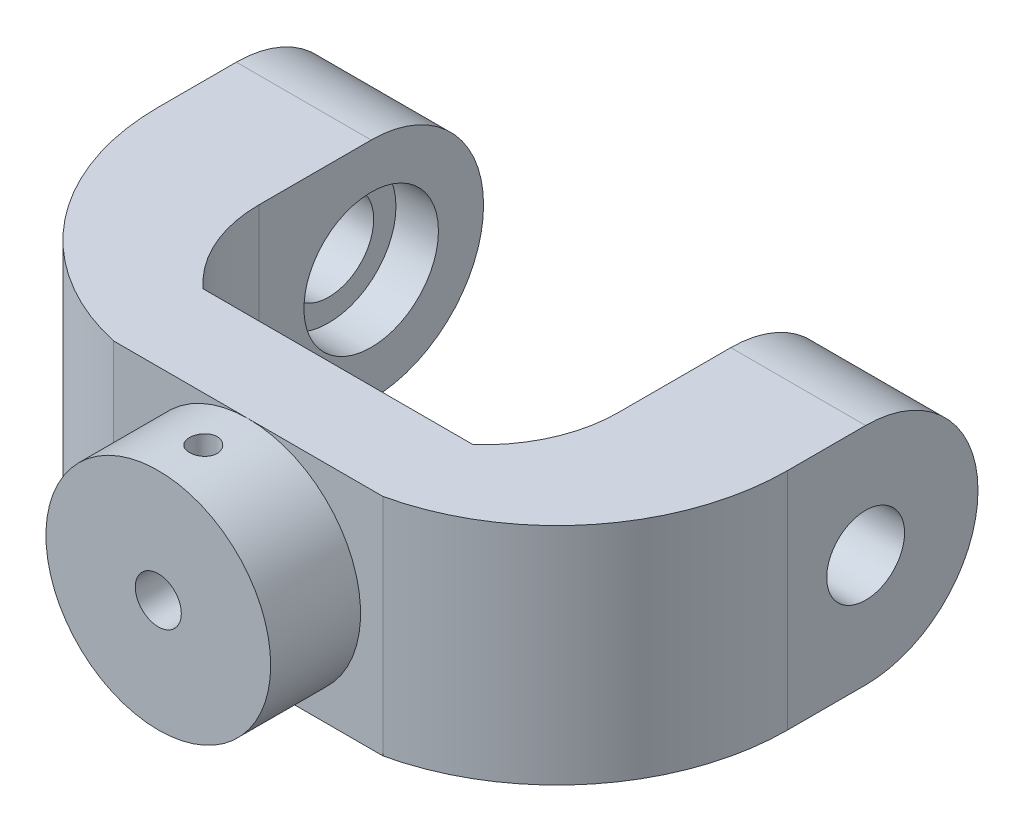
SolidWorks part; units mm, degrees
material "PLA"
ref_plane "Front Plane" through (0, 0, 0) normal (0, 0, 1) x (1, 0, 0)
ref_plane "Top Plane" through (0, 0, 0) normal (0, 1, 0) x (1, 0, 0)
ref_plane "Right Plane" through (0, 0, 0) normal (1, 0, 0) x (0, 0, -1)
sketch "Sketch1" plane through (0, 0, 0) normal (0, 0, 1) x (1, 0, 0)
  line L1 (-19.05, -15.875) -> (19.05, -15.875)
  line L2 (-19.05, -15.875) -> (-19.05, 15.875)
  line L3 (-19.05, 15.875) -> (19.05, 15.875)
  line L4 (19.05, -15.875) -> (19.05, 15.875)
  line L5 (-19.05, -15.875) -> (19.05, 15.875) construction
  line L6 (-19.05, 15.875) -> (19.05, -15.875) construction
  circle A0 centre (0, 0) radius 15.875
  circle A2 centre (0, 0) radius 3.25
  dimension "D1" = 31.75
  dimension "D3" = 6.5
  dimension "D4" = 31.75
  dimension "D5" = 38.1
extrude "Boss-Extrude1" add sketch "Sketch1" along normal blind 12.7 contours A0 region at (-15.426, 0, 0)
extrude "Boss-Extrude2" add sketch "Sketch1<3>" against normal blind 12.7 contours A0 | A0 | A0 L3 L2 L1 region at (-18.6797, 0, 0) region at (11.4871, -11.4871, 0) region at (-15.426, 0, 0)
sketch "Sketch1<3>" plane through (0, 0, 0) normal (0, 0, 1) x (1, 0, 0) same geometry as "Sketch1"
ref_plane "Plane1" through (0, 15.875, 0) normal (0, 1, 0) x (1, 0, 0)
sketch "Sketch4" plane through (0, 15.875, 0) normal (0, 1, 0) x (1, 0, 0)
  line L0 (-15.875, -12.7) -> (15.875, -12.7) construction
  line L1 (0, 0) -> (15.875, 0) construction
  line L2 (-15.875, -12.7) -> (15.875, -12.7)
  line L3 (0, 0) -> (15.875, 0)
  line L4 (0, 0) -> (0, -12.7) construction
  circle A0 centre (0, -6.35) radius 1.95
  point P4 (0, -9.525)
  dimension "D1" = 3.9
extrude "Cut-Extrude1" cut sketch "Sketch4" against normal up to surface (12.625 mm away) contours A0 L4 | L4 A0 region at (0.8276, 15.875, 6.35) region at (-0.8276, 15.875, 6.35) up to face at (3.25, 0, 12.7)
sketch "Sketch6" plane through (0, 15.875, 0) normal (0, 1, 0) x (1, 0, 0)
  line L5 (-19.05, 0) -> (0, 0)
  line L6 (0, 0) -> (19.05, 0)
  line L7 (19.05, 0) -> (19.05, 12.7)
  line L8 (19.05, 12.7) -> (-19.05, 12.7)
  line L9 (-19.05, 12.7) -> (-19.05, 0)
  line L10 (-19.05, 0) -> (0, 0)
  line L11 (0, 0) -> (19.05, 0)
  line L12 (19.05, 0) -> (19.05, 12.7)
  line L13 (19.05, 12.7) -> (-19.05, 12.7)
  line L14 (-19.05, 12.7) -> (-19.05, 0)
  dimension "D1" = 0
sketch "Sketch7" plane through (0, 15.875, 0) normal (0, 1, 0) x (1, 0, 0)
  line L0 (-44.45, 58.649) -> (-25.4, 58.649)
  line L1 (-19.05, 0) -> (0, 0) construction
  line L2 (-44.45, 31.75) -> (-44.45, 58.649)
  line L3 (-25.4, 26.899) -> (-25.4, 58.649)
  line L9 (-19.05, 0) -> (0, 0)
  line L10 (0, 0) -> (19.05, 0)
  line L11 (19.05, 0) -> (19.05, 12.7)
  line L12 (19.05, 12.7) -> (-19.05, 12.7)
  line L13 (-19.05, 12.7) -> (-19.05, 0)
  line L14 (-19.05, 0) -> (0, 0)
  line L15 (0, 0) -> (19.05, 0)
  line L16 (19.05, 0) -> (19.05, 12.7)
  line L17 (19.05, 12.7) -> (-19.05, 12.7)
  arc A0 (-19.05, 0) -> (-44.45, 31.75) centre (-11.9062, 31.75) cw
  arc A1 (-19.05, 12.7) -> (-25.4, 26.899) centre (-6.35, 26.899) cw
  line M7 (-19.05, 12.7) -> (-19.05, 0)
  dimension "D1" = 31.75
  dimension "D2" = 31.75
  dimension "D4" = 19.05
  dimension "D3" = 44.45
  dimension "D5" = 19.05
  dimension "D6" = 0
extrude "Boss-Extrude3" add sketch "Sketch7" against normal up to surface (31.75 mm away) contours A1 L3 L0 L2 A0 M7 region at (-33.015, 15.875, -31.5973) up to face at (0, -15.875, -5.08)
fillet "Fillet1" radius 15.875 2 edges at (-34.925, -15.875, -58.649) (-34.925, 15.875, -58.649)
sketch "Sketch8" plane through (-25.4, 0, 0) normal (1, 0, 0) x (0, 0, -1)
  line L3 (26.899, -15.875) -> (42.774, -15.875)
  line L4 (42.774, 15.875) -> (26.899, 15.875)
  line L5 (26.899, 15.875) -> (26.899, -15.875)
  line L6 (26.899, -15.875) -> (42.774, -15.875)
  line L7 (42.774, 15.875) -> (26.899, 15.875)
  line L8 (26.899, 15.875) -> (26.899, -15.875)
  circle A0 centre (42.774, 0) radius 9.5
  circle A1 centre (42.774, 0) radius 6.35
  arc A2 (42.774, -15.875) -> (58.649, 0) centre (42.774, 0) ccw
  arc A3 (58.649, 0) -> (42.774, 15.875) centre (42.774, 0) ccw
  arc A4 (42.774, -15.875) -> (58.649, 0) centre (42.774, 0) ccw
  arc A5 (58.649, 0) -> (42.774, 15.875) centre (42.774, 0) ccw
  dimension "D2" = 19
  dimension "D3" = 12.7
  dimension "D1" = 0
extrude "Cut-Extrude3" cut sketch "Sketch8" against normal through all contours A1 region at (-25.4, 0, -42.774)
extrude "Cut-Extrude4" cut sketch "Sketch8<3>" against normal blind 6 contours A0 A1 region at (-25.4, 0, -33.5427)
sketch "Sketch8<3>" plane through (-25.4, 0, 0) normal (1, 0, 0) x (0, 0, -1) same geometry as "Sketch8"
mirror "Mirror1" about plane through (0, 0, 0) normal (1, 0, 0) of bodies 107
sketch "Sketch9" plane through (44.45, 0, 0) normal (1, 0, 0) x (0, 0, -1)
  line L3 (42.774, 15.875) -> (31.75, 15.875)
  line L4 (31.75, 15.875) -> (31.75, -15.875)
  line L5 (31.75, -15.875) -> (42.774, -15.875)
  line L6 (42.774, 15.875) -> (31.75, 15.875)
  line L7 (31.75, 15.875) -> (31.75, -15.875)
  line L8 (31.75, -15.875) -> (42.774, -15.875)
  circle A0 centre (42.774, 0) radius 6.35 construction
  circle A1 centre (42.774, 0) radius 6.35
  arc A2 (58.649, 0) -> (42.774, 15.875) centre (42.774, 0) ccw
  arc A3 (42.774, -15.875) -> (58.649, 0) centre (42.774, 0) ccw
  arc A4 (58.649, 0) -> (42.774, 15.875) centre (42.774, 0) ccw
  arc A5 (42.774, -15.875) -> (58.649, 0) centre (42.774, 0) ccw
  circle A6 centre (42.774, 0) radius 5.5
  circle M8 centre (42.774, 0) radius 6.35
  dimension "D2" = 11
  dimension "D1" = 0
extrude "Boss-Extrude4" add sketch "Sketch9" against normal up to surface (13.05 mm away) contours A6 M8 region at (44.45, 0, -36.6036) up to face at (31.4, 0, -49.124)
sketch "Sketch10" plane through (-44.45, 0, 0) normal (-1, 0, 0) x (0, 0, 1)
  line L0 (-42.774, 0) -> (-33.57, 0) construction
  line L3 (-42.774, -15.875) -> (-31.75, -15.875)
  line L4 (-31.75, -15.875) -> (-31.75, 15.875)
  line L5 (-31.75, 15.875) -> (-42.774, 15.875)
  line L6 (-42.774, -15.875) -> (-31.75, -15.875)
  line L7 (-31.75, -15.875) -> (-31.75, 15.875)
  line L8 (-31.75, 15.875) -> (-42.774, 15.875)
  circle A0 centre (-42.774, 0) radius 6.35 construction
  circle A1 centre (-42.774, 0) radius 6.35
  arc A2 (-42.774, 15.875) -> (-58.649, 0) centre (-42.774, 0) ccw
  arc A3 (-58.649, 0) -> (-42.774, -15.875) centre (-42.774, 0) ccw
  arc A4 (-42.774, 15.875) -> (-58.649, 0) centre (-42.774, 0) ccw
  arc A5 (-58.649, 0) -> (-42.774, -15.875) centre (-42.774, 0) ccw
  circle A6 centre (-42.774, 12.7) radius 1.95
  circle A7 centre (-42.774, -12.7) radius 1.95
  dimension "D2" = 3.9
  dimension "D3" = 12.7
  dimension "D1" = 0
extrude "Cut-Extrude5" cut sketch "Sketch10" against normal blind 10.16 contours A6 | A7 region at (-44.45, 12.7, -42.774) region at (-44.45, -12.7, -42.774)
ref_plane "Plane2" through (0, 0, -76.2) normal (0, 0, 1) x (1, 0, 0)
sketch "Sketch11" plane through (0, 0, -76.2) normal (0, 0, 1) x (1, 0, 0)
  line L0 (44.45, 0) -> (25.4, 0) construction
  line L1 (44.45, 0) -> (25.4, 0)
  circle A0 centre (35.3811, 0) radius 1.95
  dimension "D1" = 3.9
extrude "Cut-Extrude6" cut sketch "Sketch11" along normal up to surface (27.926 mm away) contours L1 A0 | L1 A0 region at (35.3811, -0.8276, -76.2) region at (35.3811, 0.8276, -76.2) up to face at (44.45, 0, -48.274)
